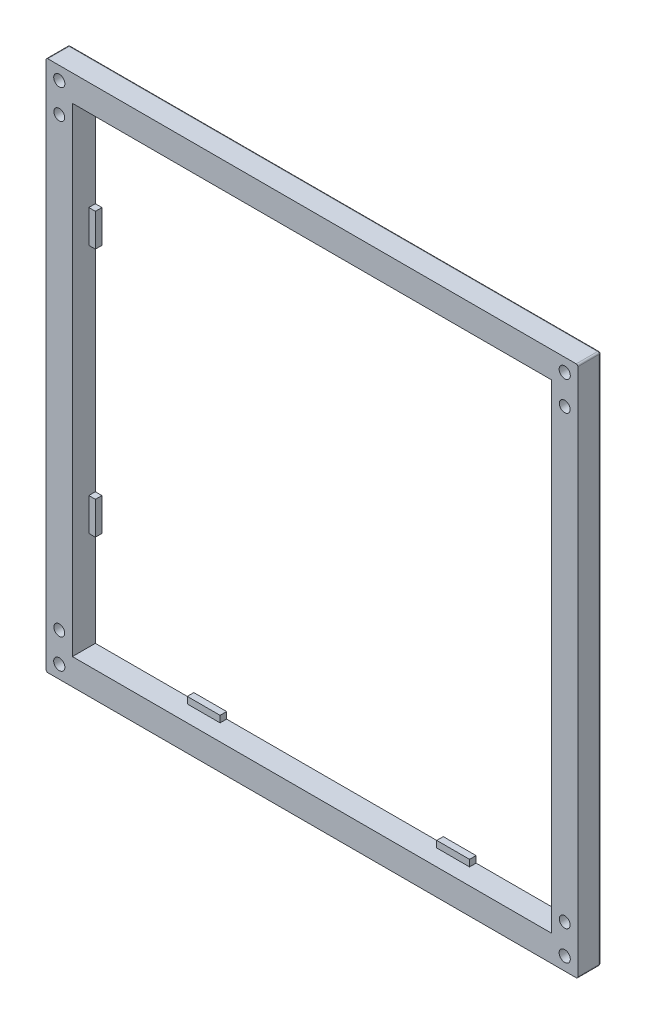
SolidWorks part; units mm, degrees
ref_plane "Спереди" through (0, 0, 0) normal (0, 0, 1) x (1, 0, 0)
ref_plane "Сверху" through (0, 0, 0) normal (0, 1, 0) x (1, 0, 0)
ref_plane "Справа" through (0, 0, 0) normal (1, 0, 0) x (0, 0, -1)
other "Configuration Table"
sketch "Эскиз1" plane through (0, 0, 0) normal (0, 0, 1) x (1, 0, 0)
  line L1 (-73, 73) -> (73, 73)
  line L2 (-73, 73) -> (-73, -73)
  line L3 (-73, -73) -> (73, -73)
  line L4 (73, 73) -> (73, -73)
  line L5 (-73, 73) -> (73, -73) construction
  line L6 (-73, -73) -> (73, 73) construction
  line L7 (-81, 81) -> (81, 81)
  line L8 (-81, 81) -> (-81, -81)
  line L9 (-81, -81) -> (81, -81)
  line L10 (81, 81) -> (81, -81)
  line L11 (-81, 81) -> (81, -81) construction
  line L12 (-81, -81) -> (81, 81) construction
  point P0 (0, 0)
  point P6 (0, 0)
  dimension "D1" = 162
  dimension "D2" = 162
  dimension "D3" = 146
  dimension "D4" = 146
extrude "Основная рамка" add sketch "Эскиз1" along normal blind 7
sketch "Эскиз2" plane through (0, 0, 0) normal (0, 0, -1) x (-1, 0, 0)
  line L1 (-43, 74) -> (-33, 74)
  line L2 (-43, 74) -> (-43, 71)
  line L3 (-43, 71) -> (-33, 71)
  line L4 (-33, 74) -> (-33, 71)
  line L5 (-81, -81) -> (-81, 81) construction
  line L6 (-81, 81) -> (81, 81) construction
  dimension "D1" = 10
  dimension "D2" = 3
  dimension "D3" = 38
  dimension "D4" = 7
extrude "Упор" add sketch "Эскиз2" against normal blind 2
mirror "Зеркальный упор" about plane through (0, 0, 0) normal (1, 0, 0) of "Упор"
ref_axis "Ось1" through (0, 0, -80.9) along (0, 0, 1)
pattern_circular "Оставшиеся упоры" count 4 over 360 about axis through (0, 0, -80.9) along (0, 0, 1) of "Упор", "Зеркальный упор"
sketch "Эскиз3" plane through (0, 0, 7) normal (0, 0, 1) x (1, 0, 0)
  line L0 (-81, 81) -> (-81, -81) construction
  line L1 (81, 81) -> (-81, 81) construction
  circle A0 centre (-77, 77) radius 1.7
  dimension "D1" = 3.4
  dimension "D2" = 4
  dimension "D3" = 4
extrude "Вырез для штифта" cut sketch "Эскиз3" against normal through all
mirror "Зеркальный вырез" about plane through (0, 0, 0) normal (1, 0, 0) of "Вырез для штифта"
mirror "Зеркальные нижние вырезы" about plane through (0, 0, 0) normal (0, 1, 0) of "Вырез для штифта", "Зеркальный вырез"
sketch "Эскиз4" plane through (0, 0, 7) normal (0, 0, 1) x (1, 0, 0)
  line L0 (-81, 81) -> (-81, -81) construction
  line L1 (81, 81) -> (-81, 81) construction
  circle A0 centre (-77, 68) radius 1.65
  dimension "D1" = 3.3
  dimension "D2" = 4
  dimension "D3" = 13
extrude "Вырез для направляющих" cut sketch "Эскиз4" against normal blind 3.5
mirror "Зеркальный вырез для напр." about plane through (0, 0, 0) normal (1, 0, 0) of "Вырез для направляющих"
mirror "Зеркальные нижние вырезы для напр." about plane through (0, 0, 0) normal (0, 1, 0) of "Вырез для направляющих", "Зеркальный вырез для напр."
sketch "Эскиз5" plane through (0, 0, 0) normal (0, 0, -1) x (-1, 0, 0)
  line L1 (-73.6514, 77) -> (-75.3257, 79.9)
  line L2 (-75.3257, 79.9) -> (-78.6743, 79.9)
  line L3 (-78.6743, 79.9) -> (-80.3486, 77)
  line L4 (-80.3486, 77) -> (-78.6743, 74.1)
  line L5 (-78.6743, 74.1) -> (-75.3257, 74.1)
  line L6 (-75.3257, 74.1) -> (-73.6514, 77)
  circle A0 centre (-77, 77) radius 2.9 construction
  circle A1 centre (-77, 77) radius 1.7 construction
  dimension "D1" = 5.8
extrude "Карман головки" cut sketch "Эскиз5" against normal blind 2.6
mirror "Зеркальные карманы" about plane through (0, 0, 0) normal (1, 0, 0) of "Карман головки" second plane through (0, 0, 0) second plane normal (0, 1, 0)
fillet "Скругление1" radius 0.5 4 edges at (0, -81, 0) (-81, 0, 0) (81, 0, 0) (0, 81, 0)
fillet "Скругление2" radius 0.5 8 edges at (80.8536, -80.8536, 0.1464) (-80.8536, -80.8536, 0.1464) (-80.8536, 80.8536, 0.1464) (80.8536, 80.8536, 0.1464) (81, -81, 3.75) (-81, -81, 3.75) (-81, 81, 3.75) (81, 81, 3.75)
